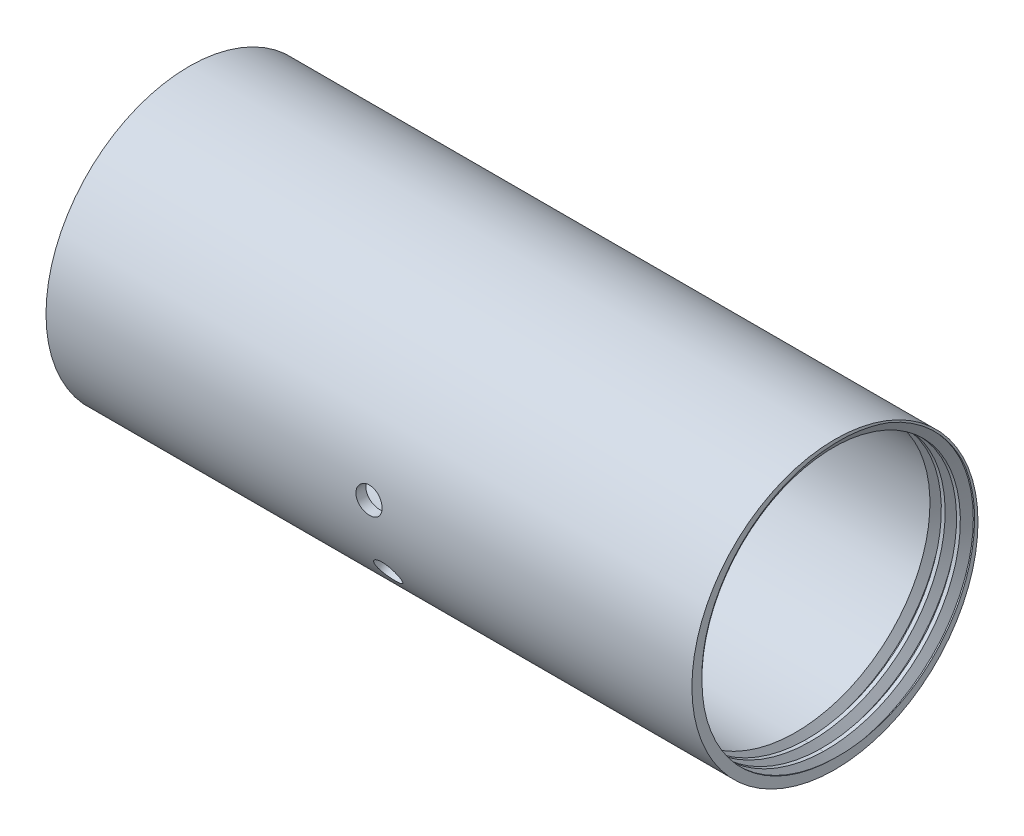
SolidWorks part; units mm, degrees
material "Custom Plastic"
ref_plane "Front Plane" through (0, 0, 0) normal (0, 0, 1) x (1, 0, 0)
ref_plane "Top Plane" through (0, 0, 0) normal (0, 1, 0) x (1, 0, 0)
ref_plane "Right Plane" through (0, 0, 0) normal (1, 0, 0) x (0, 0, -1)
sketch "Sketch1" plane through (0, 0, 0) normal (1, 0, 0) x (0, 0, -1)
  circle A0 centre (0, 0) radius 35
  circle A1 centre (0, 0) radius 37.65
  dimension "D1" = 75.3
  dimension "D2" = 70
extrude "Boss-Extrude1" add sketch "Sketch1" along normal mid plane 170 contours A1 A0 region at (0, 0, 36.5851)
thread "Thread2" pitch 4 method cut profile "Thread Profile2" start angle 0, offset 11, length 20, pitch 4, diameter 70
ref_plane "Plane2" through (96, 0, 35) normal (0, -1, 0) x (0, 0, 1)
sketch "Thread Profile2" plane through (96, 0, 35) normal (0, -1, 0) x (0, 0, 1)
  line L0 (0, 0) -> (0, 4) construction
  line L1 (0, 0) -> (2.1651, 1.25)
  line L2 (2.1651, 1.25) -> (2.1651, 1.75)
  line L3 (2.1651, 1.75) -> (0, 3)
  line L4 (2.1651, 1.5) -> (0, 1.5) construction
  line L11 (0, 0) -> (0, 3)
  point P2 (0, 0)
  dimension "Pitch" = 4
  dimension "Profile_Angle" = 60
  dimension "Profile_Land" = 0.5
  dimension "Profile_Height" = 2.1651
thread "Thread3" pitch 4 method cut profile "Thread Profile3" start angle 0, offset 11, length 20, pitch 4, diameter 70
ref_plane "Plane3" through (-96, 0, -35) normal (0, -1, 0) x (0, 0, -1)
sketch "Thread Profile3" plane through (-96, 0, -35) normal (0, -1, 0) x (0, 0, -1)
  line L0 (0, 0) -> (0, 4) construction
  line L1 (0, 0) -> (2.1651, 1.25)
  line L2 (2.1651, 1.25) -> (2.1651, 1.75)
  line L3 (2.1651, 1.75) -> (0, 3)
  line L4 (2.1651, 1.5) -> (0, 1.5) construction
  line L11 (0, 0) -> (0, 3)
  point P2 (0, 0)
  dimension "Pitch" = 4
  dimension "Profile_Angle" = 60
  dimension "Profile_Land" = 0.5
  dimension "Profile_Height" = 2.1651
ref_plane "Plane4" through (0, -37.65, 0) normal (0, -1, 0) x (-1, 0, 0)
sketch "Sketch2" plane through (0, -37.65, 0) normal (0, -1, 0) x (-1, 0, 0)
  circle A0 centre (0, 0) radius 3.45
  dimension "D1" = 6.9
extrude "Cut-Extrude1" cut sketch "Sketch2" against normal up to surface (2.8205 mm away) up to face at (-82.375, -14.9372, -23.6872)
ref_axis "Axis1" through (85, 0, 0) along (-1, 0, 0)
pattern_circular "CirPattern1" count 4 every 30 about axis through (85, 0, 0) along (-1, 0, 0) of "Cut-Extrude1"
